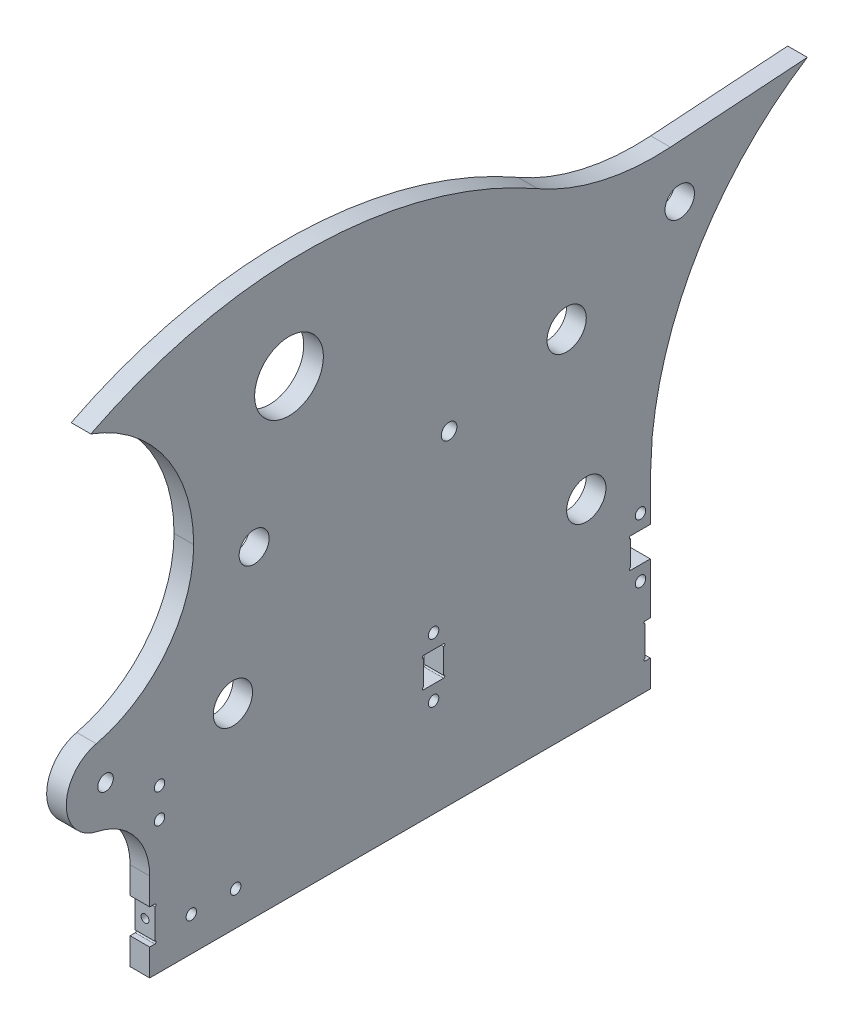
SolidWorks part; units mm, degrees
material "6061-T6 (SS)"
ref_plane "Front Plane" through (0, 0, 0) normal (0, 0, 1) x (1, 0, 0)
ref_plane "Top Plane" through (0, 0, 0) normal (0, 1, 0) x (1, 0, 0)
ref_plane "Right Plane" through (0, 0, 0) normal (1, 0, 0) x (0, 0, -1)
sketch "Sketch1" plane through (0, 0, 0) normal (1, 0, 0) x (0, 0, -1)
  line L0 (0, 44.45) -> (0, 0) construction
  line L1 (-279.4, 44.45) -> (279.4, 44.45)
  line L2 (-279.4, 44.45) -> (-279.4, -44.45)
  line L3 (-279.4, -44.45) -> (279.4, -44.45)
  line L4 (279.4, 44.45) -> (279.4, -44.45)
  line L5 (0, 0) -> (279.4, 0) construction
  dimension "D1" = 558.8
  dimension "D2" = 88.9
extrude "Boss-Extrude1" add sketch "Sketch1" along normal blind 12.7 contours L4 L1 L2 L3 region at (0, 0, 0)
sketch "Sketch2" plane through (12.7, 0, 0) normal (1, 0, 0) x (0, 0, -1)
  line L0 (-279.4, -44.45) -> (279.4, -44.45) construction
  line L1 (-279.4, 44.45) -> (-226.9595, 103.6106)
  line L2 (82.55, 44.45) -> (53.2287, 97.8348)
  line L3 (-203.2, 114.3) -> (25.4, 114.3)
  line L4 (-279.4, 44.45) -> (82.55, 44.45)
  line L5 (-279.4, 44.45) -> (279.4, 44.45) construction
  line L6 (279.4, 44.45) -> (279.4, -44.45) construction
  line L7 (-279.4, 44.45) -> (-318.8009, 0) construction
  line L8 (-318.8009, 0) -> (-279.4, -44.45) construction
  line L9 (-279.4, 44.45) -> (-279.4, -44.45) construction
  line L10 (-279.4, -44.45) -> (-279.4, 0) construction
  line L11 (-279.4, 0) -> (-318.8009, 0) construction
  circle A0 centre (-203.2, 82.55) radius 12.7
  circle A1 centre (25.4, 82.55) radius 12.7
  circle A2 centre (-203.2, 82.55) radius 31.75
  circle A3 centre (25.4, 82.55) radius 31.75
  line M2 (279.4, 44.45) -> (-279.4, 44.45)
  dimension "D1" = 25.4
  dimension "D2" = 63.5
  dimension "D3" = 127
  dimension "D4" = 127
  dimension "D5" = 228.6
  dimension "D6" = 254
  dimension "D7" = 196.85
extrude "Boss-Extrude2" add sketch "Sketch2" against normal blind 12.7 contours A3 L3 A2 L1 L2 M2 | A2 A0 | A3 A1 region at (12.7, 75.2348, 94.7711) region at (12.7, 110.6856, 215.8582) region at (12.7, 90.2167, -55.2842)
sketch "Sketch3" plane through (12.7, 0, 0) normal (1, 0, 0) x (0, 0, -1)
  line L0 (-279.4, -44.45) -> (-318.8009, 0)
  line L1 (-318.8009, 0) -> (-279.4, 44.45)
  line L2 (-279.4, 44.45) -> (-279.4, -44.45)
  line L3 (-318.8009, 0) -> (-279.4, 0) construction
  line L4 (-279.4, 44.45) -> (-226.9595, 103.6106) construction
extrude "Boss-Extrude3" add sketch "Sketch3" against normal blind 12.7
sketch "Sketch4" plane through (12.7, 0, 0) normal (1, 0, 0) x (0, 0, -1)
  line L0 (82.55, 44.45) -> (106.9639, 0)
  line L1 (106.9639, 0) -> (82.55, -44.45)
  line L2 (-279.4, -44.45) -> (279.4, -44.45) construction
  line L3 (0, 0) -> (106.9639, 0) construction
  line L4 (82.55, 44.45) -> (53.2287, 97.8348) construction
  line L5 (82.55, 44.45) -> (279.4, 44.45)
  line L6 (279.4, 44.45) -> (279.4, -44.45)
  line L7 (279.4, -44.45) -> (82.55, -44.45)
  line L8 (82.55, 44.45) -> (82.55, -44.45) construction
extrude "Cut-Extrude1" cut sketch "Sketch4" against normal through all
sketch "Sketch5" plane through (12.7, 0, 0) normal (1, 0, 0) x (0, 0, -1)
  line L0 (-257.0386, -44.45) -> (-257.0386, 69.677)
  line L1 (-279.4, -44.45) -> (82.55, -44.45) construction
  line L2 (-318.8009, 0) -> (-226.9595, 103.6106) construction
  line L4 (-257.0386, -44.45) -> (-279.4, -44.45)
  line L5 (-279.4, -44.45) -> (-318.8009, 0)
  line L6 (-318.8009, 0) -> (-257.0386, 69.677)
  line L7 (66.8114, 73.1049) -> (66.8114, -44.45)
  line L8 (106.9639, 0) -> (53.2287, 97.8348) construction
  line L9 (66.8114, -44.45) -> (82.55, -44.45)
  line L10 (82.55, -44.45) -> (106.9639, 0)
  line L11 (106.9639, 0) -> (66.8114, 73.1049)
  dimension "D1" = 323.85
extrude "Cut-Extrude2" cut sketch "Sketch5" against normal through all
sketch "Sketch6" plane through (0, 0, 0) normal (-1, 0, 0) x (0, 0, 1)
  line L0 (151.3516, 227.5219) -> (-41.9303, 109.6574)
  line L1 (228.6, 184.15) -> (228.6, 101.6)
  line L2 (-25.4, 114.3) -> (203.2, 114.3)
  circle A0 centre (177.8, 184.15) radius 22.225
  circle A1 centre (177.8, 184.15) radius 50.8
  arc A2 (-25.4, 114.3) -> (-53.2287, 97.8348) centre (-25.4, 82.55) ccw construction
  arc A3 (226.9595, 103.6106) -> (203.2, 114.3) centre (203.2, 82.55) ccw construction
  arc A4 (-41.9303, 109.6574) -> (-25.4, 114.3) centre (-25.4, 82.55) cw
  arc A5 (228.6, 101.6) -> (203.2, 114.3) centre (203.2, 82.55) ccw
  arc M6 (226.9595, 103.6106) -> (203.2, 114.3) centre (203.2, 82.55) ccw
  line M7 (203.2, 114.3) -> (-25.4, 114.3)
  arc M8 (-25.4, 114.3) -> (-53.2287, 97.8348) centre (-25.4, 82.55) ccw
  dimension "D1" = 101.6
  dimension "D3" = 44.45
  dimension "D4" = 101.6
  dimension "D2" = 25.4
extrude "Boss-Extrude4" add sketch "Sketch6" against normal blind 12.7 contours A1 L0 L1 M8 M7 M6 | A1 A0 region at (0, 143.2204, 103.515) region at (0, 227.1928, 201.9668)
fillet "Fillet1" radius 25.4 1 edges at (6.35, 101.7599, 228.6)
sketch "Sketch7" plane through (12.7, 0, 0) normal (1, 0, 0) x (0, 0, -1)
  line L1 (-69.7136, 131.8095) -> (-44.3136, 131.8095)
  line L2 (-69.7136, 131.8095) -> (-69.7136, 68.3095)
  line L3 (-69.7136, 68.3095) -> (-44.3136, 68.3095)
  line L4 (-44.3136, 131.8095) -> (-44.3136, 68.3095)
  line L5 (66.8114, 73.1049) -> (66.8114, -44.45) construction
  line L6 (-38.4716, 100.0595) -> (-38.4716, 68.3095) construction
  line L7 (-38.4716, 68.3095) -> (-44.3136, 68.3095) construction
  dimension "D1" = 31.75
  dimension "D2" = 63.5
  dimension "D3" = 111.125
  dimension "D4" = 25.4
extrude "Cut-Extrude3" [suppressed] cut sketch "Sketch7" against normal through all
sketch "Sketch8" plane through (12.7, 0, 0) normal (1, 0, 0) x (0, 0, -1)
  line L0 (66.8114, 73.1049) -> (72.5507, 180.7698)
  line L1 (-181.2511, 234.8326) -> (4.8268, 247.5033)
  line L2 (-181.2511, 234.8326) -> (66.8114, 73.1049)
  circle A0 centre (9.1408, 184.15) radius 63.5
  arc A1 (-151.3516, 227.5219) -> (-228.6, 184.15) centre (-177.8, 184.15) ccw construction
  line M11 (66.8114, 73.1049) -> (53.2287, 97.8348)
  arc M12 (53.2287, 97.8348) -> (41.9303, 109.6574) centre (25.4, 82.55) ccw
  line M13 (41.9303, 109.6574) -> (-151.3516, 227.5219)
  arc M14 (-151.3516, 227.5219) -> (-228.6, 184.15) centre (-177.8, 184.15) ccw
extrude "Boss-Extrude5" add sketch "Sketch8" against normal blind 12.7 contours A0 L1 M14 M13 | A0 M13 | A0 L0 M13 M12 M11 region at (12.7, 119.7708, -56.2638) region at (12.7, 188.0889, -11.5428) region at (12.7, 218.2036, 84.1163)
sketch "Sketch9" plane through (12.7, 0, 0) normal (1, 0, 0) x (0, 0, -1)
  line L0 (66.8114, 73.1049) -> (66.8114, -44.45) construction
  line L1 (-257.0386, -44.45) -> (66.8114, -44.45) construction
  circle A0 centre (12.7, 184.15) radius 12.7
  dimension "D1" = 228.6
  dimension "D2" = 25.4
  dimension "D3" = 54.1114
extrude "Cut-Extrude4" cut sketch "Sketch9" against normal through all
sketch "Sketch10" plane through (0, 0, 0) normal (-1, 0, 0) x (0, 0, 1)
  line L0 (-4.8268, 247.5033) -> (-168.4114, 258.6423)
  line L1 (-66.8114, 73.1049) -> (-66.8114, -44.45) construction
  line L2 (181.2511, 234.8326) -> (-4.8268, 247.5033) construction
  line L3 (-72.5507, 180.7698) -> (-66.8114, 73.1049)
  line L4 (257.0386, -44.45) -> (-66.8114, -44.45) construction
  arc A0 (-168.4114, 258.6423) -> (-66.8114, 73.1049) centre (-287.0215, 73.1049) cw
  arc A1 (-4.8268, 247.5033) -> (-72.5507, 180.7698) centre (-9.1408, 184.15) ccw
  circle A2 centre (-85.8614, 219.075) radius 9.525
  line M2 (-72.5507, 180.7698) -> (-66.8114, 73.1049)
  arc M11 (-4.8268, 247.5033) -> (-72.5507, 180.7698) centre (-9.1408, 184.15) ccw
  dimension "D1" = 101.6
  dimension "D2" = 19.05
  dimension "D3" = 263.525
  dimension "D4" = 19.05
extrude "Boss-Extrude6" add sketch "Sketch10" against normal blind 12.7 contours L0 A0 A2 M2 M11 region at (0, 231.0213, -55.3266)
sketch "Sketch11" plane through (12.7, 0, 0) normal (1, 0, 0) x (0, 0, -1)
  line L0 (-257.0386, -44.45) -> (66.8114, -44.45) construction
  line L1 (66.8114, 73.1049) -> (66.8114, -44.45) construction
  line L2 (-181.2511, 234.8326) -> (168.4114, 258.6423) construction
  line L3 (-228.6, 184.15) -> (-228.6, 111.3968) construction
  line L4 (-181.2511, 234.8326) -> (28.7114, 249.1297)
  arc A1 (-228.6, 184.15) -> (-295.1386, 279.4) centre (-330.0445, 184.15) ccw
  arc A2 (-295.1386, 279.4) -> (28.7114, 249.1297) centre (-157.2044, 7.5964) cw
  arc A3 (-228.6, 184.15) -> (-181.2511, 234.8326) centre (-177.8, 184.15) cw
  dimension "D4" = 323.85
  dimension "D7" = 304.8
  dimension "D5" = 361.95
  dimension "D6" = 38.1
extrude "Boss-Extrude7" add sketch "Sketch11" against normal blind 12.7
fillet "Fillet2" radius 152.4 1 edges at (6.35, 249.1297, -28.7114)
sketch "Sketch12" plane through (0, 0, 0) normal (-1, 0, 0) x (0, 0, 1)
  line L0 (-66.8114, 73.1049) -> (-66.8114, -44.45) construction
  line L1 (-63.6364, -26.9875) -> (-66.8114, -26.9875)
  line L2 (-63.6364, -26.9875) -> (-63.6364, -4.7625)
  line L3 (-63.6364, -4.7625) -> (-66.8114, -4.7625)
  line L4 (-66.8114, -26.9875) -> (-66.8114, -4.7625)
  line L5 (257.0386, -44.45) -> (257.0386, 69.677) construction
  line L6 (253.8636, -26.9875) -> (257.0386, -26.9875)
  line L7 (253.8636, -26.9875) -> (253.8636, -4.7625)
  line L8 (253.8636, -4.7625) -> (257.0386, -4.7625)
  line L9 (257.0386, -26.9875) -> (257.0386, -4.7625)
  line L10 (253.7366, -27.1145) -> (253.7366, -4.6355)
  line L11 (253.7366, -4.6355) -> (257.1656, -4.6355)
  line L12 (257.1656, -27.1145) -> (257.1656, -4.6355)
  line L13 (253.7366, -27.1145) -> (257.1656, -27.1145)
  line L14 (-63.5094, -27.1145) -> (-63.5094, -4.6355)
  line L15 (-63.5094, -4.6355) -> (-66.9384, -4.6355)
  line L16 (-66.9384, -27.1145) -> (-66.9384, -4.6355)
  line L17 (-63.5094, -27.1145) -> (-66.9384, -27.1145)
  dimension "D1" = 0.127
extrude "Cut-Extrude5" cut sketch "Sketch12" against normal through all body kept at (0, 252.6091, -79.8089)
sketch "Sketch13" plane through (0, 0, 0) normal (-1, 0, 0) x (0, 0, 1)
  line L0 (-63.5094, -27.1145) -> (-63.5094, -4.6355) construction
  line L1 (253.7366, -4.6355) -> (253.7366, -27.1145) construction
  circle A0 centre (-63.5094, -5.4292) radius 0.7937
  circle A1 centre (-63.5094, -26.3208) radius 0.7937
  circle A2 centre (253.7366, -5.4292) radius 0.7937
  circle A3 centre (253.7366, -26.3207) radius 0.7937
  dimension "D1" = 1.5875
extrude "Cut-Extrude6" cut sketch "Sketch13" against normal through all
hole_wizard "1/4-20 Tapped Hole1" positions "Sketch15" profile "Sketch14" tap size "1/4-20" standard "ANSI Inch"
sketch "Sketch15" plane through (0, 0, 253.7366) normal (0, 0, 1) x (1, 0, 0)
  point P0 (6.35, -15.875)
sketch "Sketch14" plane through (6.35, -15.875, 253.7366) normal (1, 0, 0) x (0, -1, 0)
  line L0 (0, 0) -> (0, 18.0438)
  line L1 (0, 18.0438) -> (2.5527, 16.51)
  line L2 (2.5527, 16.51) -> (2.5527, 0)
  line L5 (2.5527, 0) -> (0, 0)
  line L10 (0, 18.0438) -> (-2.5527, 16.51) construction
  line L11 (0, -6.35) -> (0, 107.95) construction
  dimension "Tap Drill Dia." = 5.1054
  dimension "Tap Drill Depth" = 16.51
  dimension "Drill Angle" = 118
hole_wizard "1/4-20 Tapped Hole2" positions "Sketch17" profile "Sketch16" tap size "1/4-20" standard "ANSI Inch"
sketch "Sketch17" plane through (0, 0, -63.5094) normal (0, 0, -1) x (-1, 0, 0)
  point P0 (-6.35, -15.875)
sketch "Sketch16" plane through (6.35, -15.875, -63.5094) normal (1, 0, 0) x (0, 1, 0)
  line L0 (0, 0) -> (0, 18.0438)
  line L1 (0, 18.0438) -> (2.5527, 16.51)
  line L2 (2.5527, 16.51) -> (2.5527, 0)
  line L5 (2.5527, 0) -> (0, 0)
  line L10 (0, 18.0438) -> (-2.5527, 16.51) construction
  line L11 (0, -6.35) -> (0, 107.95) construction
  dimension "Tap Drill Dia." = 5.1054
  dimension "Tap Drill Depth" = 16.51
  dimension "Drill Angle" = 118
sketch "Sketch18" plane through (12.7, 0, 0) normal (1, 0, 0) x (0, 0, -1)
  line L0 (-257.0386, -4.6355) -> (-257.0386, 69.677) construction
  line L1 (-257.0386, -44.45) -> (66.8114, -44.45) construction
  line L17 (-253.7366, -27.1145) -> (-257.0386, -27.1145)
  line L18 (-257.0386, -27.1145) -> (-257.0386, -44.45)
  line L19 (-257.0386, -44.45) -> (66.8114, -44.45)
  line L20 (66.8114, -44.45) -> (66.8114, -27.1145)
  line L21 (66.8114, -27.1145) -> (63.5094, -27.1145)
  line L22 (63.5094, -25.527) -> (63.5094, -6.223)
  line L23 (63.5094, -4.6355) -> (66.8114, -4.6355)
  line L24 (66.8114, -4.6355) -> (66.8114, 73.1049)
  line L25 (66.8114, 73.1049) -> (68.0594, 96.5159)
  line L26 (168.4114, 258.6423) -> (79.8089, 252.6091)
  line L27 (-228.6, 184.15) -> (-228.6, 111.3968)
  line L28 (-234.9924, 94.5483) -> (-257.0386, 69.677)
  line L29 (-257.0386, 69.677) -> (-257.0386, -4.6355)
  line L30 (-257.0386, -4.6355) -> (-253.7366, -4.6355)
  line L31 (-253.7366, -6.223) -> (-253.7366, -25.527)
  line L32 (-253.7366, -27.1145) -> (-257.0386, -27.1145)
  line L33 (-257.0386, -27.1145) -> (-257.0386, -44.45)
  line L34 (-257.0386, -44.45) -> (66.8114, -44.45)
  line L35 (66.8114, -44.45) -> (66.8114, -27.1145)
  line L36 (66.8114, -27.1145) -> (63.5094, -27.1145)
  line L37 (63.5094, -25.527) -> (63.5094, -6.223)
  line L38 (63.5094, -4.6355) -> (66.8114, -4.6355)
  line L39 (66.8114, -4.6355) -> (66.8114, 73.1049)
  line L40 (66.8114, 73.1049) -> (68.0594, 96.5159)
  line L41 (168.4114, 258.6423) -> (79.8089, 252.6091)
  line L42 (-228.6, 184.15) -> (-228.6, 111.3968)
  line L43 (-234.9924, 94.5483) -> (-257.0386, 69.677)
  line L44 (-257.0386, 69.677) -> (-257.0386, -4.6355)
  line L45 (-257.0386, -4.6355) -> (-253.7366, -4.6355)
  line L46 (-253.7366, -6.223) -> (-253.7366, -25.527)
  arc A0 (-257.0386, 12.7) -> (-290.9023, 54.5317) centre (-299.8077, 12.7) ccw
  circle A1 centre (-285.6136, 79.375) radius 25.4
  arc A2 (-291.5967, 104.0603) -> (-228.6, 184.15) centre (-311.0087, 184.15) ccw
  arc A3 (-228.6, 184.15) -> (-295.1386, 279.4) centre (-330.0445, 184.15) ccw construction
  arc A13 (-253.7366, -27.1145) -> (-253.7366, -25.527) centre (-253.7366, -26.3207) ccw
  arc A14 (63.5094, -25.527) -> (63.5094, -27.1145) centre (63.5094, -26.3208) ccw
  arc A15 (63.5094, -4.6355) -> (63.5094, -6.223) centre (63.5094, -5.4292) ccw
  arc A16 (168.4114, 258.6423) -> (68.0594, 96.5159) centre (287.0215, 73.1049) ccw
  arc A17 (-6.0978, 272.3034) -> (79.8089, 252.6091) centre (69.4555, 404.657) ccw
  arc A18 (-6.0978, 272.3034) -> (-295.1386, 279.4) centre (-157.2044, 7.5964) ccw
  arc A19 (-228.6, 184.15) -> (-295.1386, 279.4) centre (-330.0445, 184.15) ccw
  arc A20 (-234.9924, 94.5483) -> (-228.6, 111.3968) centre (-254, 111.3968) ccw
  arc A21 (-253.7366, -6.223) -> (-253.7366, -4.6355) centre (-253.7366, -5.4292) ccw
  arc A22 (-253.7366, -27.1145) -> (-253.7366, -25.527) centre (-253.7366, -26.3207) ccw
  arc A23 (63.5094, -25.527) -> (63.5094, -27.1145) centre (63.5094, -26.3208) ccw
  arc A24 (63.5094, -4.6355) -> (63.5094, -6.223) centre (63.5094, -5.4292) ccw
  arc A25 (168.4114, 258.6423) -> (68.0594, 96.5159) centre (287.0215, 73.1049) ccw
  arc A26 (-6.0978, 272.3034) -> (79.8089, 252.6091) centre (69.4555, 404.657) ccw
  arc A27 (-6.0978, 272.3034) -> (-295.1386, 279.4) centre (-157.2044, 7.5964) ccw
  arc A28 (-228.6, 184.15) -> (-295.1386, 279.4) centre (-330.0445, 184.15) ccw
  arc A29 (-234.9924, 94.5483) -> (-228.6, 111.3968) centre (-254, 111.3968) ccw
  arc A30 (-253.7366, -6.223) -> (-253.7366, -4.6355) centre (-253.7366, -5.4292) ccw
  line M42 (-228.6, 184.15) -> (-228.6, 111.3968)
  arc M43 (-228.6, 111.3968) -> (-234.9924, 94.5483) centre (-254, 111.3968) cw
  line M44 (-234.9924, 94.5483) -> (-257.0386, 69.677)
  line M45 (-257.0386, 69.677) -> (-257.0386, -4.6355)
  dimension "D1" = 57.15
  dimension "D2" = 50.8
  dimension "D3" = 28.575
  dimension "D4" = 123.825
  dimension "D5" = 0
extrude "Boss-Extrude8" add sketch "Sketch18" against normal up to surface (12.7 mm away) contours A2 A1 A0 M45 M44 M43 M42 | A1 region at (12.7, 98.8268, 251.0034) region at (12.7, 79.375, 285.6136) up to face at (0, 61.0151, 91.7271)
hole_wizard "3/8 Clearance Hole1" positions "Sketch20" profile "Sketch19" hole size "3/8" standard "ANSI Inch"
sketch "Sketch20" plane through (0, 0, 0) normal (-1, 0, 0) x (0, 0, 1)
  line L0 (257.0386, -44.45) -> (-66.8114, -44.45) construction
  line L1 (257.0386, -4.6355) -> (257.0386, 12.7) construction
  point P0 (285.6136, 79.375)
  point P3 (63.3636, 165.1)
  dimension "D1" = 209.55
  dimension "D2" = 193.675
sketch "Sketch19" plane through (0, 79.375, 285.6136) normal (0, 1, 0) x (0, 0, 1)
  line L0 (0, 0) -> (0, 15.7295)
  line L1 (0, 15.7295) -> (5.0419, 12.7)
  line L2 (5.0419, 12.7) -> (5.0419, 0)
  line L5 (5.0419, 0) -> (0, 0)
  line L10 (0, 15.7295) -> (-5.0419, 12.7) construction
  line L11 (0, -6.35) -> (0, 107.95) construction
  dimension "Hole Dia." = 10.0838
  dimension "Hole Depth" = 12.7
  dimension "Drill Angle" = 118
hole_wizard "1/4 Clearance Hole1" positions "Sketch22" profile "Sketch21" hole size "1/4" standard "ANSI Inch"
sketch "Sketch22" plane through (12.7, 0, 0) normal (1, 0, 0) x (0, 0, -1)
  point P0 (-250.6886, 60.2385)
  point P2 (-250.6886, 41.1885)
  point P4 (-73.3966, 19.05)
  point P6 (-73.3966, 57.15)
  point P8 (60.4614, 57.15)
  point P10 (60.4614, 19.05)
sketch "Sketch21" plane through (12.7, 60.2385, 250.6886) normal (0, 1, 0) x (0, 0, -1)
  line L0 (0, 0) -> (0, 14.7298)
  line L1 (0, 14.7298) -> (3.3782, 12.7)
  line L2 (3.3782, 12.7) -> (3.3782, 0)
  line L5 (3.3782, 0) -> (0, 0)
  line L10 (0, 14.7298) -> (-3.3782, 12.7) construction
  line L11 (0, -6.35) -> (0, 107.95) construction
  dimension "Hole Dia." = 6.7564
  dimension "Hole Depth" = 12.7
  dimension "Drill Angle" = 118
sketch "Sketch23" plane through (0, 0, 0) normal (-1, 0, 0) x (0, 0, 1)
  line L0 (-66.8114, 73.1049) -> (-66.8114, -4.6355) construction
  line L1 (-66.8114, 28.575) -> (-54.1114, 28.575)
  line L2 (-66.8114, 28.575) -> (-66.8114, 47.625)
  line L3 (-66.8114, 47.625) -> (-54.1114, 47.625)
  line L4 (-54.1114, 28.575) -> (-54.1114, 47.625)
  line L5 (-53.9844, 28.448) -> (-53.9844, 47.752)
  line L6 (67.0466, 47.625) -> (79.7466, 47.625)
  line L7 (67.0466, 47.625) -> (67.0466, 28.575)
  line L8 (67.0466, 28.575) -> (79.7466, 28.575)
  line L9 (79.7466, 47.625) -> (79.7466, 28.575)
  line L10 (-66.9384, 47.752) -> (-53.9844, 47.752)
  line L11 (-66.9384, 28.448) -> (-66.9384, 47.752)
  line L12 (-66.9384, 28.448) -> (-53.9844, 28.448)
  line L13 (79.8736, 47.752) -> (79.8736, 28.448)
  line L14 (66.9196, 28.448) -> (79.8736, 28.448)
  line L15 (66.9196, 47.752) -> (66.9196, 28.448)
  line L16 (66.9196, 47.752) -> (79.8736, 47.752)
  dimension "D1" = 0.127
extrude "Cut-Extrude7" cut sketch "Sketch23" against normal through all
sketch "Sketch24" plane through (12.7, 0, 0) normal (1, 0, 0) x (0, 0, -1)
  line L0 (-79.8736, 28.448) -> (-79.8736, 47.752) construction
  line L1 (-66.9196, 47.752) -> (-66.9196, 28.448) construction
  line L2 (53.9844, 28.448) -> (53.9844, 47.752) construction
  circle A0 centre (-79.8736, 46.9583) radius 0.7937
  circle A1 centre (-66.9196, 46.9583) radius 0.7937
  circle A2 centre (-66.9196, 29.2418) radius 0.7937
  circle A3 centre (-79.8736, 29.2418) radius 0.7937
  circle A4 centre (53.9844, 29.2417) radius 0.7937
  circle A5 centre (53.9844, 46.9582) radius 0.7937
  dimension "D1" = 1.5875
extrude "Cut-Extrude8" cut sketch "Sketch24" against normal through all
hole_wizard "1/4 Clearance Hole2" positions "Sketch26" profile "Sketch25" hole size "1/4" standard "ANSI Inch" end condition through all
sketch "Sketch26" plane through (12.7, 0, 0) normal (1, 0, 0) x (0, 0, -1)
  point P0 (-230.1146, -22.225)
  point P2 (-201.4126, -22.225)
sketch "Sketch25" plane through (12.7, -22.225, 230.1146) normal (0, 1, 0) x (0, 0, -1)
  line L0 (0, 0) -> (0, 12.7)
  line L1 (0, 12.7) -> (3.3782, 12.7)
  line L2 (3.3782, 12.7) -> (3.3782, 0)
  line L5 (3.3782, 0) -> (0, 0)
  line L11 (0, -6.35) -> (0, 107.95) construction
  dimension "Thru Hole Dia." = 6.7564
  dimension "Thru Hole Depth" = 12.7
sketch "Sketch27" plane through (12.7, 0, 0) normal (1, 0, 0) x (0, 0, -1)
  circle A0 centre (-177.8, 184.15) radius 22.225
extrude "Boss-Extrude9" add sketch "Sketch27" against normal up to surface (12.7 mm away) up to face at (0, -22.225, 226.7364)
sketch "Sketch28" plane through (12.7, 0, 0) normal (1, 0, 0) x (0, 0, -1)
  line L0 (-166.9051, 247.65) -> (12.7, 184.15) construction
  line L1 (-257.0386, -44.45) -> (66.8114, -44.45) construction
  circle A0 centre (-166.9051, 247.65) radius 22.225
  dimension "D1" = 44.45
  dimension "D2" = 190.5
  dimension "D3" = 292.1
extrude "Cut-Extrude9" cut sketch "Sketch28" against normal through all
sketch "Sketch29" plane through (12.7, 0, 0) normal (1, 0, 0) x (0, 0, -1)
  line L0 (-257.0386, -44.45) -> (66.8114, -44.45) construction
  line L1 (-257.0386, -44.45) -> (-257.0386, -27.1145) construction
  circle A0 centre (-189.5033, 163.3126) radius 9.6837
  dimension "D1" = 19.3675
  dimension "D2" = 207.7626
  dimension "D3" = 67.5353
extrude "Cut-Extrude10" cut sketch "Sketch29" against normal through all
